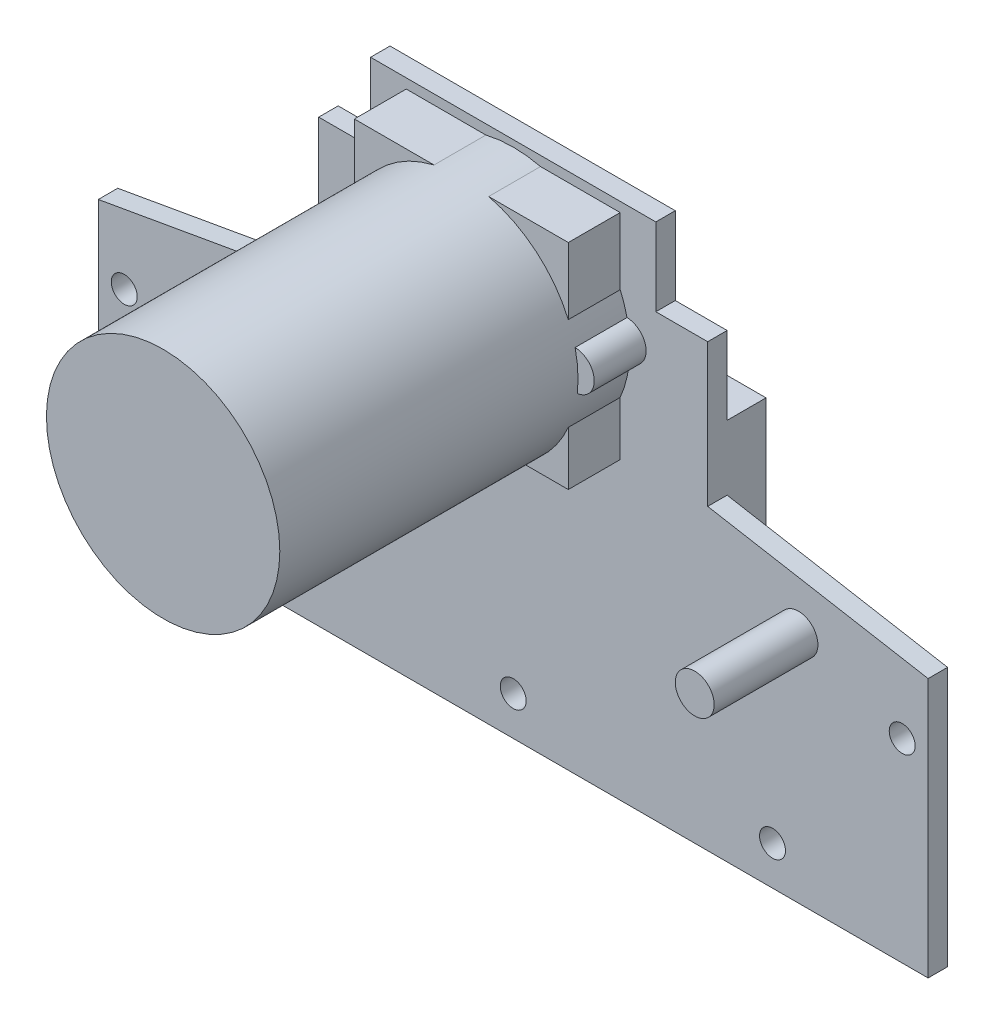
SolidWorks part; units mm, degrees
material "Nickel"
ref_plane "Front Plane" through (0, 0, 0) normal (0, 0, 1) x (1, 0, 0)
ref_plane "Top Plane" through (0, 0, 0) normal (0, 1, 0) x (1, 0, 0)
ref_plane "Right Plane" through (0, 0, 0) normal (1, 0, 0) x (0, 0, -1)
sketch "Sketch1" plane through (0, 0, 0) normal (0, 0, 1) x (1, 0, 0)
  line L0 (-32, 0) -> (32, 0)
  line L1 (-1015.4659, 23) -> (48984.5341, 23) construction
  line L2 (-15, 23) -> (15, 23)
  line L3 (-32, 0) -> (-32, 20)
  line L4 (-32, 20) -> (-15, 23)
  line L5 (32, 0) -> (32, 20)
  line L6 (32, 20) -> (15, 23)
  line L7 (-15, 23) -> (-15, 34)
  line L8 (-15, 34) -> (15, 34)
  line L9 (15, 34) -> (15, 23)
  line L10 (-1006.9308, 40) -> (48993.0692, 40) construction
  line L11 (-11, 40) -> (11, 40)
  line L12 (-11, 40) -> (-11, 34)
  line L13 (11, 40) -> (11, 34)
  line L14 (0, 34) -> (0, 40) construction
  dimension "D1" = 64
  dimension "D2" = 23
  dimension "D3" = 30
  dimension "D4" = 20
  dimension "D5" = 11
  dimension "D6" = 6
  dimension "D7" = 22
extrude "Boss-Extrude1" add sketch "Sketch1" along normal blind 1.5 contours L5 L6 L2 L4 L3 L0 | L9 L8 L7 L2 | L13 L11 L12 L8 region at (0, 11.1232, 0) region at (0, 28.5, 0) region at (0, 37, 0)
sketch "Sketch2" plane through (0, 0, 1.5) normal (0, 0, 1) x (1, 0, 0)
  line L0 (-1024.4669, 3) -> (48975.5331, 3) construction
  line L1 (-32, 0) -> (32, 0) construction
  line L2 (-20, 3) -> (20, 3)
  line L3 (-32, 0) -> (-32, 20) construction
  line L4 (0, -997) -> (0, 49003) construction
  circle A0 centre (-20, 3) radius 1
  circle A1 centre (20, 3) radius 1
  circle A2 centre (0, 3) radius 1
  circle A3 centre (-30, 15) radius 1
  circle A4 centre (30, 15) radius 1
  dimension "D3" = 2
  dimension "D1" = 40
  dimension "D2" = 3
  dimension "D5" = 15
  dimension "D6" = 2
extrude "Cut-Extrude1" cut sketch "Sketch2" against normal blind 5 contours A3 | A1 | A0 | A2 | A4 region at (20, 3.9717, 1.5) region at (-30, 15, 1.5)
sketch "Sketch3" plane through (0, 0, 1.5) normal (0, 0, 1) x (1, 0, 0)
  line L0 (0, 40) -> (0, 0) construction
  line L1 (-11, 40) -> (11, 40) construction
  line L2 (-32, 0) -> (32, 0) construction
  line L4 (-8.5, 39) -> (8.5, 39)
  line L5 (-8.5, 39) -> (-8.5, 22)
  line L6 (-8.5, 22) -> (8.5, 22)
  line L7 (8.5, 39) -> (8.5, 22)
  circle A0 centre (0, 30.5) radius 9
  circle A1 centre (0, 30.5) radius 8.5
  dimension "D1" = 18
  dimension "D2" = 17
  dimension "D3" = 17
  dimension "D4" = 1
extrude "Boss-Extrude2" add sketch "Sketch3" along normal blind 27 contours A0
sketch "Sketch4" plane through (0, 0, 28.5) normal (0, 0, 1) x (1, 0, 0)
  circle A0 centre (0, 31) radius 9
sketch "Sketch5" plane through (0, 0, 0) normal (0, 0, -1) x (-1, 0, 0)
  line L0 (32, 0) -> (-32, 0) construction
  line L1 (-15, 7) -> (13, 7)
  line L2 (-15, 7) -> (-15, 28)
  line L3 (-15, 28) -> (13, 28)
  line L4 (13, 7) -> (13, 28)
  line L5 (32, 0) -> (32, 20) construction
  line L6 (15, 23) -> (15, 34) construction
  dimension "D1" = 28
  dimension "D2" = 19
  dimension "D3" = 30
  dimension "D4" = 7
extrude "Boss-Extrude3" add sketch "Sketch5" along normal blind 3
sketch "Sketch6" plane through (0, 0, 1.5) normal (0, 0, 1) x (1, 0, 0)
  line L0 (22, 18) -> (-22, 18) construction
  line L1 (0, 0) -> (0, 18) construction
  line L2 (-32, 0) -> (32, 0) construction
  circle A0 centre (22, 18) radius 1.5
  circle A1 centre (-22, 18) radius 1.5
  dimension "D2" = 3
  dimension "D1" = 44
  dimension "D3" = 18
extrude "Boss-Extrude4" add sketch "Sketch6" along normal blind 8
sketch "Sketch7" plane through (0, 0, 1.5) normal (0, 0, 1) x (1, 0, 0)
  line L0 (-10.25, 41.25) -> (-10.25, 20.75) construction
  line L1 (-8.25, 39.25) -> (8.25, 39.25)
  line L2 (-8.25, 39.25) -> (-8.25, 22.75)
  line L3 (-8.25, 22.75) -> (8.25, 22.75)
  line L4 (8.25, 39.25) -> (8.25, 22.75)
  line L5 (-8.25, 39.25) -> (8.25, 22.75) construction
  line L6 (-8.25, 22.75) -> (8.25, 39.25) construction
  line L7 (-10.25, 20.75) -> (10.25, 20.75) construction
  line L8 (10.25, 41.25) -> (10.25, 20.75) construction
  line L9 (-10.25, 41.25) -> (10.25, 41.25) construction
  circle A0 centre (0, 31) radius 9 construction
  circle A2 centre (-8.75, 31) radius 1.5
  circle A3 centre (8.75, 31) radius 1.5
  point P0 (0, 31)
  dimension "D3" = 3
  dimension "D1" = 16.5
  dimension "D2" = 2
extrude "Boss-Extrude5" add sketch "Sketch7" along normal blind 4 contours A2 | L2 L3 L4 L1 | A3
